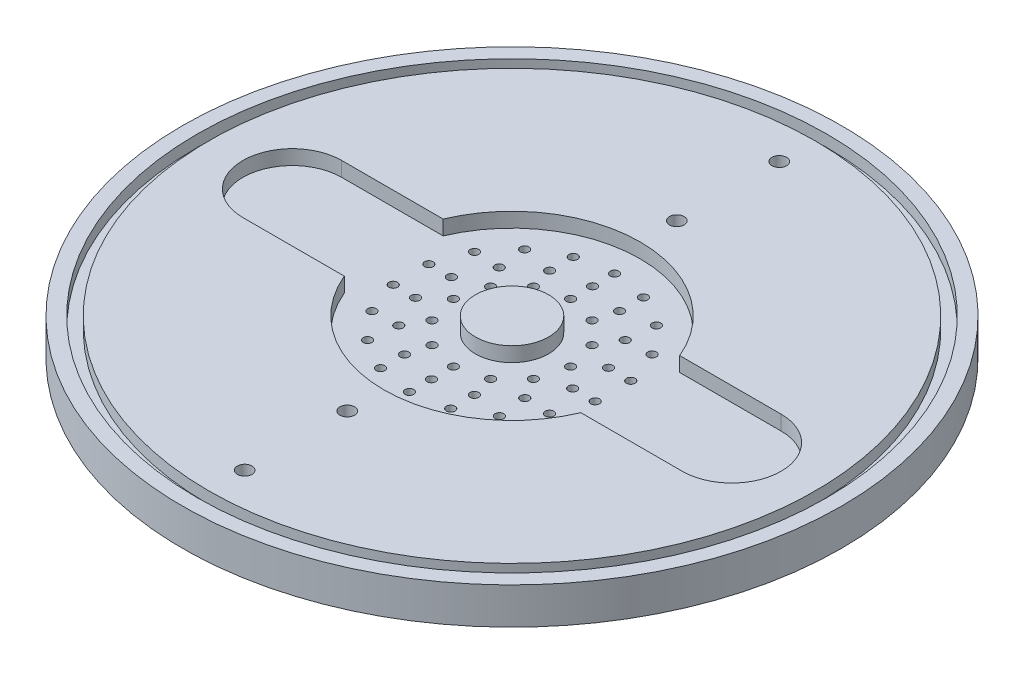
SolidWorks part; units mm, degrees
material "AISI 304"
ref_plane "Front Plane" through (0, 0, 0) normal (0, 0, 1) x (1, 0, 0)
ref_plane "Top Plane" through (0, 0, 0) normal (0, 1, 0) x (1, 0, 0)
ref_plane "Right Plane" through (0, 0, 0) normal (1, 0, 0) x (0, 0, -1)
sketch "Main Shape Profile" plane through (0, 0, 0) normal (0, 0, 1) x (1, 0, 0)
  line L1 (57.15, 0) -> (57.15, 6.35)
  line L2 (57.15, 6.35) -> (0, 6.35)
  line L5 (0, 6.35) -> (0, 0)
  line L6 (0, 0) -> (57.15, 0)
  line L7 (0, 0) -> (0, -50000) construction
  point P1 (0.2017, 8.89)
  point P4 (0, 0)
  dimension "Kerosene Plate Outer Diameter" = 114.3
  dimension "Kerosene Plate Thickness" = 6.35
revolve "Main Shape" add sketch "Main Shape Profile" angle 360 about L7
sketch "O Rings Profile" plane through (0, 0, 0) normal (0, 0, 1) x (1, 0, 0)
  line L0 (57.15, 6.35) -> (-57.15, 6.35) construction
  line L1 (52.578, 6.35) -> (54.61, 6.35)
  line L2 (52.578, 6.35) -> (52.578, 4.318)
  line L3 (52.578, 4.318) -> (54.61, 4.318)
  line L4 (54.61, 6.35) -> (54.61, 4.318)
  line L5 (-57.15, 0) -> (57.15, 0) construction
  line L6 (52.578, 0) -> (54.61, 0)
  line L7 (52.578, 0) -> (52.578, 2.032)
  line L8 (52.578, 2.032) -> (54.61, 2.032)
  line L9 (54.61, 0) -> (54.61, 2.032)
  line L10 (57.15, 0) -> (57.15, 6.35) construction
  line L11 (0, 0) -> (0, -50000) construction
  dimension "O Ring Depth1" = 2.032
  dimension "O Ring Width" = 2.032
  dimension "O Ring Position" = 2.54
revolve "O-Rings Cutout" cut sketch "O Rings Profile" angle 360 about L11
sketch "Injector Well Profile" plane through (0, 6.35, 0) normal (0, 1, 0) x (1, 0, 0)
  line L0 (-38.1, 0) -> (38.1, 0) construction
  line L1 (-38.1, 8.575) -> (-20.5041, 8.575)
  line L2 (-38.1, -8.575) -> (-20.5041, -8.575)
  line L3 (20.5041, 8.575) -> (38.1, 8.575)
  line L4 (20.5041, -8.575) -> (38.1, -8.575)
  arc A0 (-20.5041, -8.575) -> (20.5041, -8.575) centre (0, 0) ccw
  circle A1 centre (0, 0) radius 6.35
  arc A2 (-38.1, 8.575) -> (-38.1, -8.575) centre (-38.1, 0) ccw
  arc A3 (38.1, -8.575) -> (38.1, 8.575) centre (38.1, 0) ccw
  arc A4 (20.5041, 8.575) -> (-20.5041, 8.575) centre (0, 0) ccw
  point P6 (0, 0)
  point P14 (-20.5041, 7.196)
  point P15 (-19.3055, -11.018)
  point P16 (37.066, -8.575)
  dimension "Kerosene Mainfold Diameter" = 44.45
  dimension "Slot Radius" = 17.1501
  dimension "Standoff Diameter" = 12.7
  dimension "Slot Diameter" = 76.2
extrude "Injector Well" cut sketch "Injector Well Profile" against normal blind 2.54
sketch "Dowel Holes Profile" plane through (0, 6.35, 0) normal (0, 1, 0) x (1, 0, 0)
  line L0 (0, -46.355) -> (0, -28.575) construction
  line L1 (0, -28.575) -> (0, -22.225) construction
  line L2 (0, 28.575) -> (0, 22.225) construction
  line L3 (0, 28.575) -> (0, 46.355) construction
  line L4 (0, 46.355) -> (0, 52.578) construction
  line L5 (0, -46.355) -> (0, -52.578) construction
  circle A1 centre (0, 28.575) radius 1.27
  circle A2 centre (0, 46.355) radius 1.27
  circle A3 centre (0, -46.355) radius 1.27
  circle A4 centre (0, -28.575) radius 1.27
  arc A5 (-20.5041, -8.575) -> (20.5041, -8.575) centre (0, 0) ccw construction
  arc A6 (20.5041, 8.575) -> (-20.5041, 8.575) centre (0, 0) ccw construction
  circle A7 centre (0, 0) radius 52.578 construction
  circle A8 centre (0, 0) radius 52.578 construction
  point P1 (0, 28.575)
  point P31 (0, 46.228)
  dimension "Dowel Hole Diameter" = 2.54
  dimension "Dowel Placement Inner Diameter" = 57.15
  dimension "Dowel Placement Outer Diameter" = 92.71
extrude "Dowel Holes" cut sketch "Dowel Holes Profile" against normal blind 2.54
sketch "Injector Holes" plane through (0, 3.81, 0) normal (0, 1, 0) x (1, 0, 0)
  line L0 (0, -10.16) -> (0, -13.97) construction
  line L1 (0, -13.97) -> (0, -17.78) construction
  circle A0 centre (0, 0) radius 10.16 construction
  circle A1 centre (0, 0) radius 13.97 construction
  circle A2 centre (0, 0) radius 17.78 construction
  circle A4 centre (0, -17.78) radius 0.7493
  circle A5 centre (0, -13.97) radius 0.7493
  circle A6 centre (0, -10.16) radius 0.7493
  circle A7 centre (-6.0811, -16.7077) radius 0.7493
  circle A11 centre (-11.4288, -13.6203) radius 0.7493
  circle A12 centre (-15.3979, -8.89) radius 0.7493
  circle A13 centre (-17.5099, -3.0875) radius 0.7493
  circle A22 centre (-17.5099, 3.0875) radius 0.7493
  circle A23 centre (-15.3979, 8.89) radius 0.7493
  circle A24 centre (-11.4288, 13.6203) radius 0.7493
  circle A25 centre (-6.0811, 16.7077) radius 0.7493
  circle A26 centre (0, 17.78) radius 0.7493
  circle A27 centre (6.0811, 16.7077) radius 0.7493
  circle A28 centre (11.4288, 13.6203) radius 0.7493
  circle A29 centre (15.3979, 8.89) radius 0.7493
  circle A30 centre (17.5099, 3.0875) radius 0.7493
  circle A31 centre (17.5099, -3.0875) radius 0.7493
  circle A32 centre (15.3979, -8.89) radius 0.7493
  circle A33 centre (11.4288, -13.6203) radius 0.7493
  circle A35 centre (-6.0614, -12.5865) radius 0.7493
  circle A36 centre (-10.9222, -8.7102) radius 0.7493
  circle A37 centre (-13.6197, -3.1086) radius 0.7493
  circle A38 centre (-13.6197, 3.1086) radius 0.7493
  circle A39 centre (-10.9222, 8.7102) radius 0.7493
  circle A40 centre (-6.0614, 12.5865) radius 0.7493
  circle A41 centre (0, 13.97) radius 0.7493
  circle A42 centre (6.0614, 12.5865) radius 0.7493
  circle A43 centre (10.9222, 8.7102) radius 0.7493
  circle A44 centre (13.6197, 3.1086) radius 0.7493
  circle A45 centre (13.6197, -3.1086) radius 0.7493
  circle A46 centre (10.9222, -8.7102) radius 0.7493
  circle A48 centre (-5.08, -8.7988) radius 0.7493
  circle A49 centre (-8.7988, -5.08) radius 0.7493
  circle A50 centre (-10.16, 0) radius 0.7493
  circle A51 centre (-8.7988, 5.08) radius 0.7493
  circle A52 centre (-5.08, 8.7988) radius 0.7493
  circle A53 centre (0, 10.16) radius 0.7493
  circle A54 centre (5.08, 8.7988) radius 0.7493
  circle A55 centre (8.7988, 5.08) radius 0.7493
  circle A56 centre (10.16, 0) radius 0.7493
  circle A59 centre (6.0614, -12.5865) radius 0.7493
  circle A60 centre (6.0811, -16.7077) radius 0.7493
  circle A61 centre (8.7988, -5.08) radius 0.7493
  circle A62 centre (5.08, -8.7988) radius 0.7493
  point P66 (0, 0)
  point P94 (0, 0)
  point P114 (0, 0)
  dimension "Injector Hole Diameter" = 1.4986
  dimension "Inner Ring Diameter" = 20.32
  dimension "Outer Ring Diameter" = 35.56
  dimension "Outer Ring Holes Num" = 18
  dimension "Middle Ring Holes Num" = 14
  dimension "Inner Ring Holes Num" = 12
extrude "Circular Injector Holes" cut sketch "Injector Holes" against normal through all
